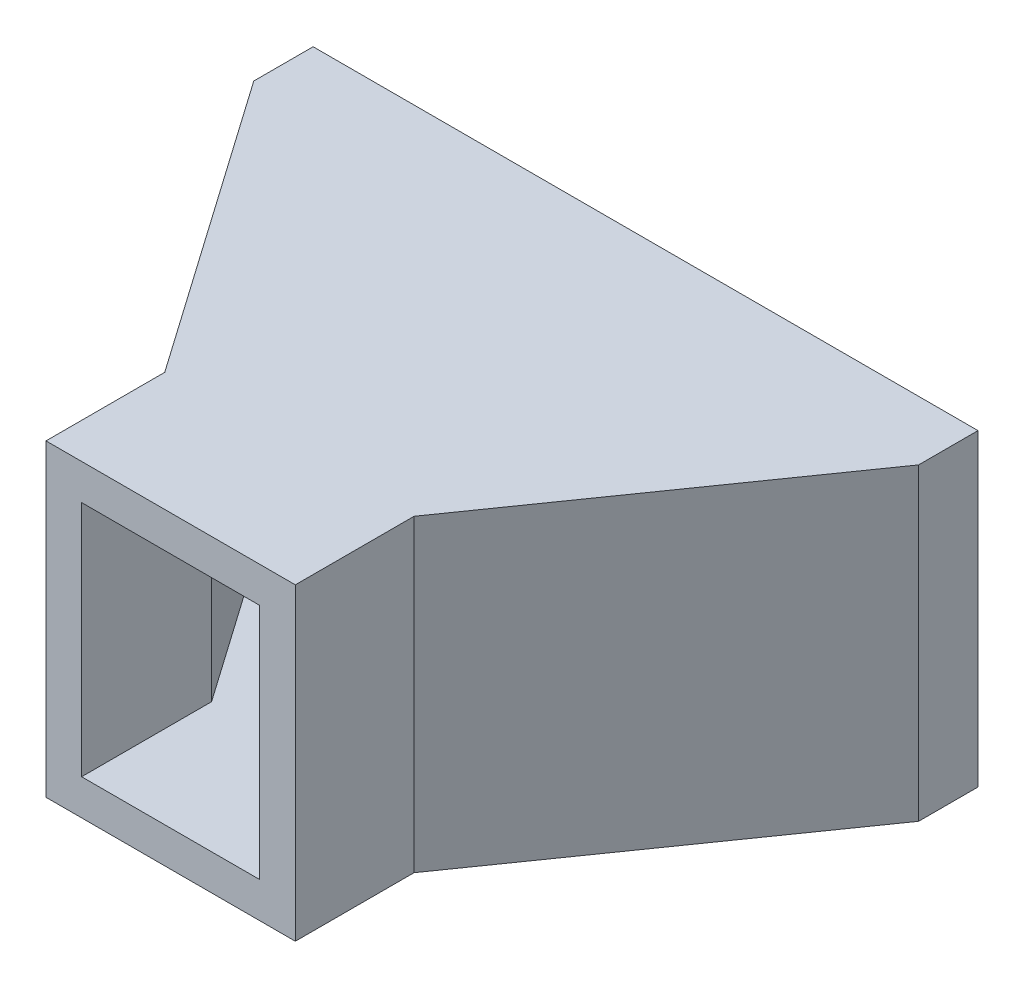
SolidWorks part; units mm, degrees
ref_plane "Alzado" through (0, 0, 0) normal (0, 0, 1) x (1, 0, 0)
ref_plane "Planta" through (0, 0, 0) normal (0, 1, 0) x (1, 0, 0)
ref_plane "Vista lateral" through (0, 0, 0) normal (1, 0, 0) x (0, 0, -1)
sketch "Croquis1" plane through (0, 0, 0) normal (0, 1, 0) x (1, 0, 0)
  line L0 (-25, 17.3913) -> (-25, 13.337)
  line L1 (-25, 13.337) -> (-7.5, -11.663)
  line L2 (-7.5, -11.663) -> (-7.5, -22.6087)
  line L3 (-7.5, -22.6087) -> (-10.5, -22.6087)
  line L4 (-10.5, -22.6087) -> (-10.5, -12.6087)
  line L5 (-10.5, -12.6087) -> (-28, 12.3913)
  line L6 (-28, 12.3913) -> (-28, 17.3913)
  line L7 (-28, 17.3913) -> (-25, 17.3913)
  line L16 (7.5, -11.663) -> (7.5, -22.6087)
  line L17 (7.5, -22.6087) -> (10.5, -22.6087)
  line L18 (10.5, -22.6087) -> (10.5, -12.6087)
  line L19 (10.5, -12.6087) -> (28, 12.3913)
  line L20 (28, 12.3913) -> (28, 17.3913)
  line L21 (28, 17.3913) -> (25, 17.3913)
  line L22 (25, 17.3913) -> (25, 13.337)
  line L23 (25, 13.337) -> (7.5, -11.663)
  line L24 (-25, 17.3913) -> (25, 17.3913) construction
  line L25 (-7.5, -22.6087) -> (7.5, -22.6087) construction
  point P10 (0, -22.6087)
  point P17 (0, 17.3913)
  dimension "D1" = 50
  dimension "D2" = 15
  dimension "D3" = 3
  dimension "D4" = 3
  dimension "D5" = 3
  dimension "D6" = 40
  dimension "D7" = 10
  dimension "D8" = 5
extrude "Saliente-Extruir1" add sketch "Croquis1" along normal blind 20
sketch "Croquis2" plane through (0, 20, 0) normal (0, 1, 0) x (1, 0, 0)
  line L0 (-10.5, -22.6087) -> (10.5, -22.6087)
  line L1 (10.5, -22.6087) -> (10.5, -12.6087)
  line L2 (10.5, -12.6087) -> (28, 12.3913)
  line L3 (28, 12.3913) -> (28, 17.3913)
  line L4 (28, 17.3913) -> (-28, 17.3913)
  line L5 (-28, 17.3913) -> (-28, 12.3913)
  line L6 (-28, 12.3913) -> (-10.5, -12.6087)
  line L7 (-10.5, -12.6087) -> (-10.5, -22.6087)
extrude "Saliente-Extruir2" add sketch "Croquis2" along normal blind 3
extrude "Saliente-Extruir3" add sketch "Croquis2<2>" against normal blind 3 from surface starting at face at (-17.75, 0, 1.1223)
sketch "Croquis2<2>" plane through (0, 20, 0) normal (0, 1, 0) x (1, 0, 0) same geometry as "Croquis2"
